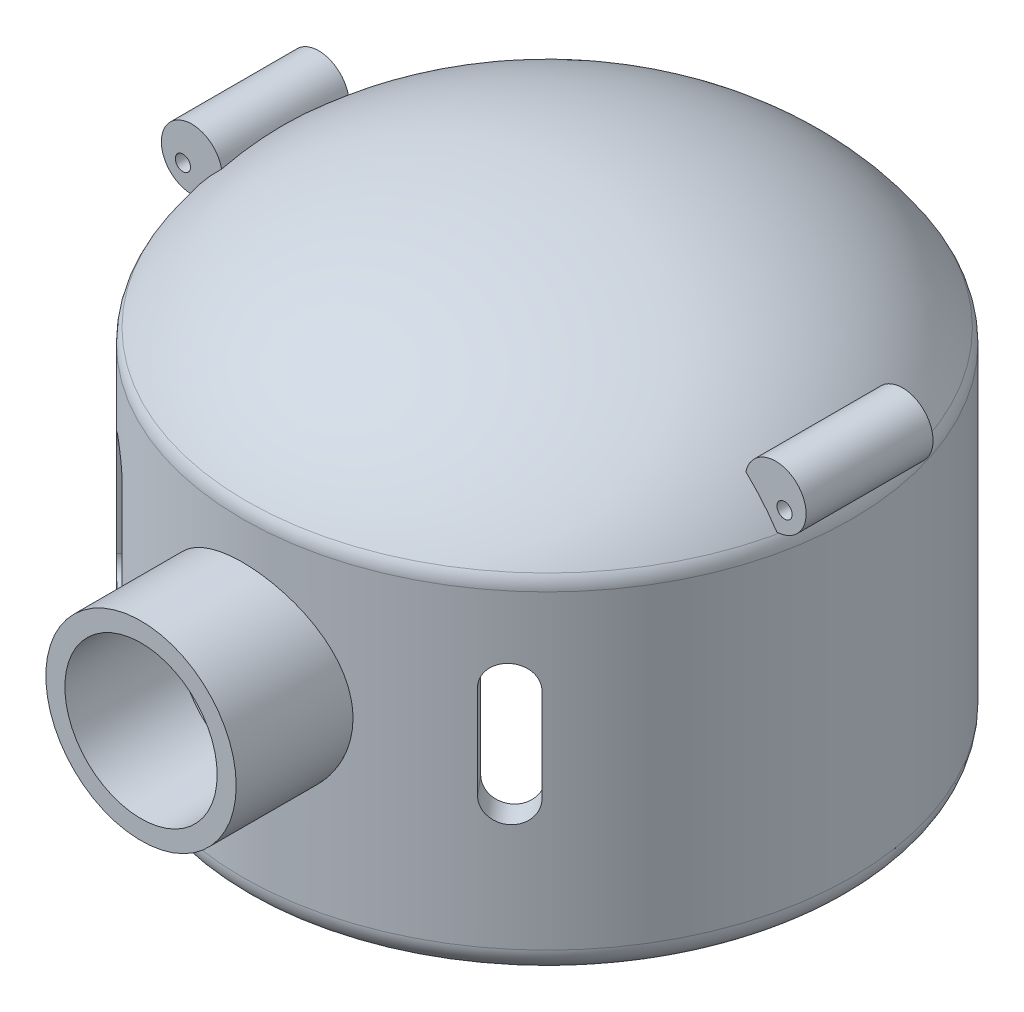
SolidWorks part; units mm, degrees
ref_plane "Front Plane" through (0, 0, 0) normal (0, 0, 1) x (1, 0, 0)
ref_plane "Top Plane" through (0, 0, 0) normal (0, 1, 0) x (1, 0, 0)
ref_plane "Right Plane" through (0, 0, 0) normal (1, 0, 0) x (0, 0, -1)
sketch "Sketch3" plane through (0, 0, 0) normal (0, 1, 0) x (1, 0, 0)
  circle A0 centre (0, 0) radius 120
  dimension "D1" = 240
extrude "Boss-Extrude1" add sketch "Sketch3" along normal blind 135
sketch "Sketch4" plane through (0, 0, 0) normal (0, 0, 1) x (1, 0, 0)
  line L0 (-120, 132.2235) -> (-120, 10) construction
  line L1 (120, 135) -> (-120, 135) construction
  line L2 (0, -107.25) -> (0, 107.25) construction
  line L3 (0, 190) -> (0, 135)
  line L4 (0, 135) -> (-120, 135)
  line L5 (120, 135) -> (-120, 135) construction
  line L6 (36.828, 190) -> (-36.828, 190) construction
  line L7 (-60, 238.923) -> (-180, 31.077) construction
  spline S0 degree 3 poles (-120, 135) (-100, 169.641) (-50, 190) (0, 190) knots 0 0 0 0 1 1 1 1
  dimension "D2" = 150
  dimension "D3" = 120
  dimension "D1" = 55
  dimension "D4" = 60
revolve "Revolve2" add sketch "Sketch4" angle 360 about L3
fillet "Fillet1" radius 10 1 edges at (0, 135, 120)
fillet "Fillet2" radius 10 1 edges at (0, 0, 120)
shell "Shell3" thickness 10 removed face at (0, 0, 110)
sketch "Sketch5" plane through (0, 0, 0) normal (0, 0, 1) x (1, 0, 0)
  line L0 (0, -104.5) -> (0, 104.5) construction
  line L1 (110, 0) -> (-110, 0) construction
  circle A0 centre (0, 80) radius 30
  circle A1 centre (0, 80) radius 37.5
  dimension "D1" = 60
  dimension "D3" = 75
  dimension "D2" = 80
extrude "Boss-Extrude2" add sketch "Sketch5" against normal up to surface (43.8105 mm away) from offset 160 up to face at (0, 10, 120)
sketch "Sketch7" plane through (0, 0, 160) normal (0, 0, 1) x (1, 0, 0)
  circle A3 centre (0, 80) radius 30 construction
  circle A4 centre (0, 80) radius 30
  circle A5 centre (0, 80) radius 65
  dimension "D1" = 130
ref_axis "Axis1" through (0, 199.5, 0) along (0, -1, 0)
ref_plane "Plane1" through (0, 0, 0) normal (-0.6428, 0, -0.766) x (0, -1, 0)
sketch "Sketch11" plane through (0, 0, 0) normal (-0.6428, 0, -0.766) x (0, -1, 0)
  line L0 (-98.5, 0) -> (-61.5, 0) construction
  line L1 (-98.5, 9) -> (-61.5, 9)
  line L2 (-98.5, -9) -> (-61.5, -9)
  line L3 (-199.5, 0) -> (9.5, 0) construction
  line L4 (-80, -22.9813) -> (-80, 22.9813) construction
  arc A0 (-98.5, 9) -> (-98.5, -9) centre (-98.5, 0) ccw
  arc A1 (-61.5, -9) -> (-61.5, 9) centre (-61.5, 0) ccw
  point P2 (-80, 0)
  point P7 (-107.5, 0)
  point P8 (-52.5, 0)
  dimension "D1" = 18
  dimension "D2" = 55
extrude "Cut-Extrude2" cut sketch "Sketch11" against normal up to next
mirror "Mirror1" about plane through (0, 0, 0) normal (1, 0, 0) of "Cut-Extrude2"
extrude "Cut-Extrude3" cut sketch "Sketch5<2>" along normal up to next contours A0 region at (0, 80, 0)
sketch "Sketch5<2>" plane through (0, 0, 0) normal (0, 0, 1) x (1, 0, 0) same geometry as "Sketch5"
ref_plane "Plane2" through (0, 150, 0) normal (0, 1, 0) x (1, 0, 0)
sketch "Sketch12" plane through (0, 150, 0) normal (0, 1, 0) x (1, 0, 0)
  line L6 (-127, 25) -> (-115, 25)
  line L7 (-127, 25) -> (-127, -25)
  line L8 (-127, -25) -> (-115, -25)
  line L9 (-115, 25) -> (-115, -25)
  line L10 (-104.5, 0) -> (104.5, 0) construction
  line L11 (0, -104.5) -> (0, 104.5) construction
  point P4 (-115, 0)
  dimension "D1" = 12
  dimension "D2" = 50
  dimension "D3" = 115
revolve "Revolve3" add sketch "Sketch12" angle 360 about L9
sketch "Sketch14" plane through (0, 0, 25) normal (0, 0, 1) x (1, 0, 0)
  line L0 (-115, 162) -> (-115, 150) construction
  line L1 (-115, 150) -> (-127, 150) construction
  circle A0 centre (-118.5, 147) radius 3
  arc A2 (-103.2616, 152.4922) -> (-115.4893, 138.01) centre (-115, 150) ccw construction
  dimension "D1" = 6
  dimension "D2" = 3
  dimension "D3" = 3.5
extrude "Cut-Extrude4" cut sketch "Sketch14" against normal up to next
mirror "Mirror4" about plane through (0, 0, 0) normal (1, 0, 0) of "Cut-Extrude4", "Revolve3"
extrude "Cut-Extrude5" cut sketch "Sketch5<3>" along normal up to surface (113.9901 mm away) contours A1 A0 | A0 region at (0, 80, 0) region at (-36.4393, 80, 0) up to face at (120, 132.2144, 0)
sketch "Sketch5<3>" plane through (0, 0, 0) normal (0, 0, 1) x (1, 0, 0) same geometry as "Sketch5"
